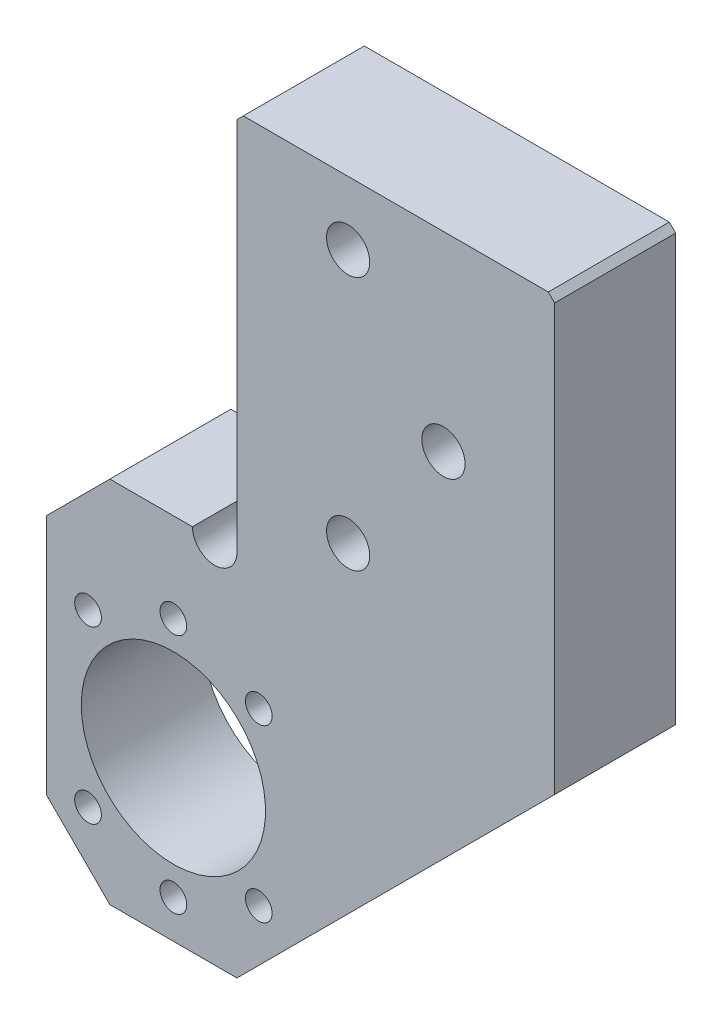
SolidWorks part; units mm, degrees
material "6061-T6 (SS)"
ref_plane "Front Plane" through (0, 0, 0) normal (0, 0, 1) x (1, 0, 0)
ref_plane "Top Plane" through (0, 0, 0) normal (0, 1, 0) x (1, 0, 0)
ref_plane "Right Plane" through (0, 0, 0) normal (1, 0, 0) x (0, 0, -1)
sketch "Sketch1" plane through (0, 0, 0) normal (0, 0, 1) x (1, 0, 0)
  line L0 (3, 33) -> (-10, 33)
  line L1 (-10, 33) -> (-20, 23)
  line L2 (-20, 23) -> (-20, -15)
  line L3 (-20, -15) -> (-10, -25)
  line L4 (-10, -25) -> (10, -25)
  line L5 (10, -25) -> (60, 25)
  line L6 (60, 25) -> (60, 93)
  line L7 (60, 93) -> (10, 93)
  line L8 (10, 93) -> (10, 33)
  line L9 (0, -10.4775) -> (0, 10.4775) construction
  line L10 (-10, -25) -> (-10, 33) construction
  line L12 (27.5, 83) -> (42.5, 83) construction
  line L13 (27.5, 83) -> (27.5, 43) construction
  line L14 (27.5, 43) -> (42.5, 43) construction
  line L15 (42.5, 83) -> (42.5, 43) construction
  line L16 (0, -19) -> (13.435, -13.435) construction
  line L17 (13.435, -13.435) -> (19, 0) construction
  line L18 (19, 0) -> (13.435, 13.435) construction
  line L19 (13.435, 13.435) -> (0, 19) construction
  line L20 (0, 19) -> (-13.435, 13.435) construction
  line L21 (-13.435, 13.435) -> (-19, 0) construction
  line L22 (-19, 0) -> (-13.435, -13.435) construction
  line L23 (-13.435, -13.435) -> (0, -19) construction
  circle A0 centre (0, 0) radius 14.5
  arc A1 (10, 33) -> (3, 33) centre (6.5, 33) cw
  circle A2 centre (0, 0) radius 17.5537 construction
  point P14 (0, -25)
  point P21 (42.5, 63)
  point P22 (27.5, 83)
  point P24 (27.5, 43)
  dimension "D1" = 29
  dimension "D6" = 3.5
  dimension "D2" = 30
  dimension "D3" = 6
  dimension "D4" = 33
  dimension "D5" = 10
  dimension "D7" = 10
  dimension "D8" = 17.5
  dimension "D9" = 10
  dimension "D10" = 17.5
  dimension "D11" = 15
  dimension "D12" = 10
  dimension "D13" = 40
  dimension "D14" = 38
extrude "Boss-Extrude1" add sketch "Sketch1" along normal mid plane 19.05
hole_wizard "M8x1.25 Tapped Hole1" positions "Sketch2" profile "Sketch3" tap size "M8x1.25" standard "ANSI Metric" end condition up to next
sketch "Sketch2" plane through (0, 0, 9.525) normal (0, 0, 1) x (1, 0, 0)
  line L0 (42.5, 83) -> (42.5, 43) construction
  point P0 (27.5, 43)
  point P3 (42.5, 63)
  point P7 (27.5, 83)
sketch "Sketch3" plane through (27.5, 43, 9.525) normal (1, 0, 0) x (0, -1, 0)
  line L0 (0, 0) -> (0, 19.05)
  line L1 (0, 19.05) -> (3.4, 19.05)
  line L2 (3.4, 19.05) -> (3.4, 0)
  line L5 (3.4, 0) -> (0, 0)
  line L11 (0, -6.35) -> (0, 107.95) construction
  dimension "Thru Tap Drill Dia." = 6.8
  dimension "Thru Tap Drill Depth" = 19.05
cosmetic thread "Hole Thread1"
cosmetic thread "Hole Thread2"
cosmetic thread "Hole Thread3"
hole_wizard " Tapped Hole0" positions "Sketch4" profile "Sketch5" tap size "M5x0.8" standard "ANSI Metric" end condition up to next
sketch "Sketch4" plane through (0, 0, 9.525) normal (0, 0, 1) x (1, 0, 0)
  point P0 (0, 19)
  point P3 (-13.435, 13.435)
  point P6 (13.435, 13.435)
  point P9 (13.435, -13.435)
  point P12 (0, -19)
  point P15 (-13.435, -13.435)
sketch "Sketch5" plane through (0, 19, 9.525) normal (1, 0, 0) x (0, -1, 0)
  line L0 (0, 0) -> (0, 19.05)
  line L1 (0, 19.05) -> (2.1, 19.05)
  line L2 (2.1, 19.05) -> (2.1, 0)
  line L5 (2.1, 0) -> (0, 0)
  line L11 (0, -6.35) -> (0, 107.95) construction
  dimension "Thru Tap Drill Dia." = 4.2
  dimension "Thru Tap Drill Depth" = 19.05
cosmetic thread "Hole Thread4"
cosmetic thread "Hole Thread5"
cosmetic thread "Hole Thread6"
cosmetic thread "Hole Thread7"
cosmetic thread "Hole Thread8"
cosmetic thread "Hole Thread9"
chamfer "Chamfer1" distance 1 2 edges at (10, 93, 0) (60, 93, 0)
